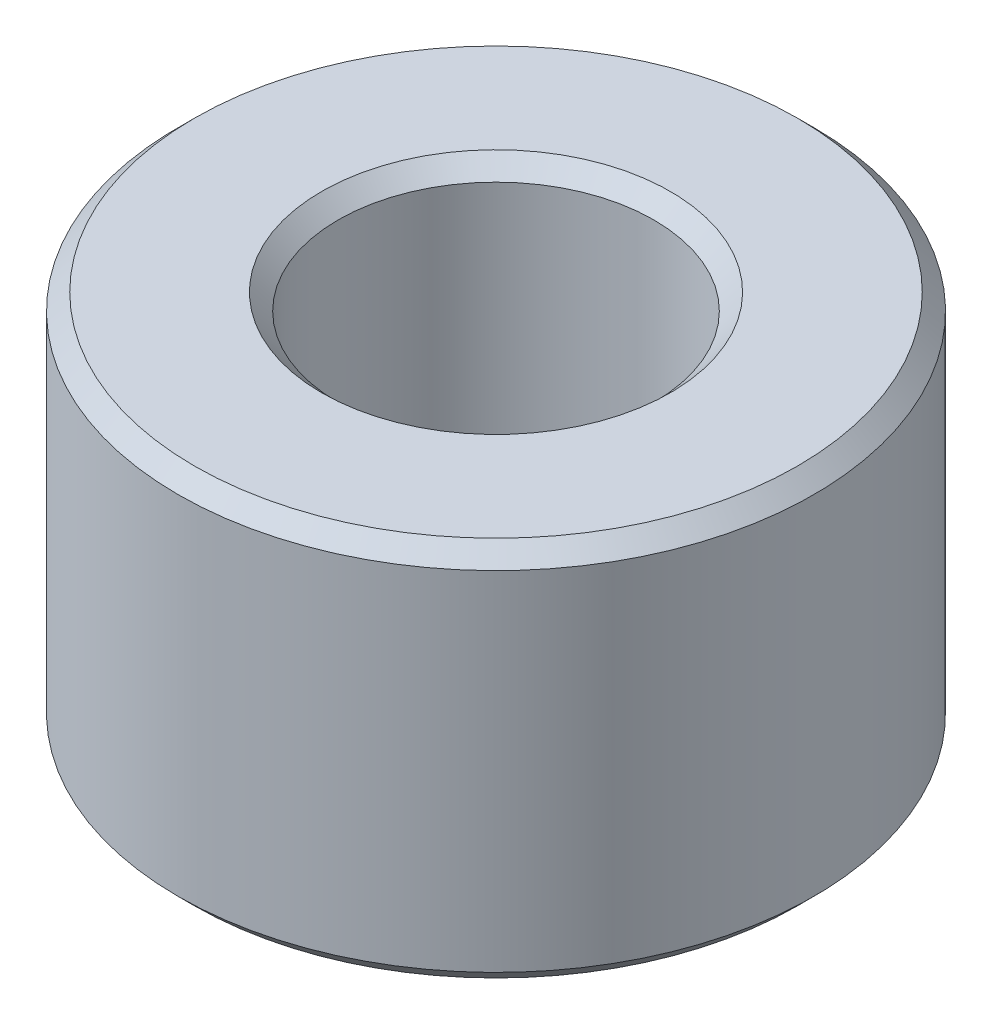
SolidWorks part; units mm, degrees
ref_plane "Front Plane" through (0, 0, 0) normal (0, 0, 1) x (1, 0, 0)
ref_plane "Top Plane" through (0, 0, 0) normal (0, 1, 0) x (1, 0, 0)
ref_plane "Right Plane" through (0, 0, 0) normal (1, 0, 0) x (0, 0, -1)
sketch "Sketch1" plane through (0, 0, 0) normal (0, 1, 0) x (1, 0, 0)
  circle A0 centre (0, 0) radius 55
  dimension "SLEEVE_OD" = 110
extrude "Boss-Extrude1" add sketch "Sketch1" along normal blind 65.9
sketch "Sketch2" plane through (0, 0, 0) normal (0, 1, 0) x (1, 0, 0)
  circle A0 centre (0, 0) radius 27.3275
  dimension "BORE_D" = 54.6549
extrude "Cut-Extrude1" cut sketch "Sketch2" along normal through all
chamfer "Chamfer1" distance 2.8457 angle 45 4 edges at (0, 65.9, 27.3275) (0, 0, 27.3275) (0, 0, 55) (0, 65.9, 55)
